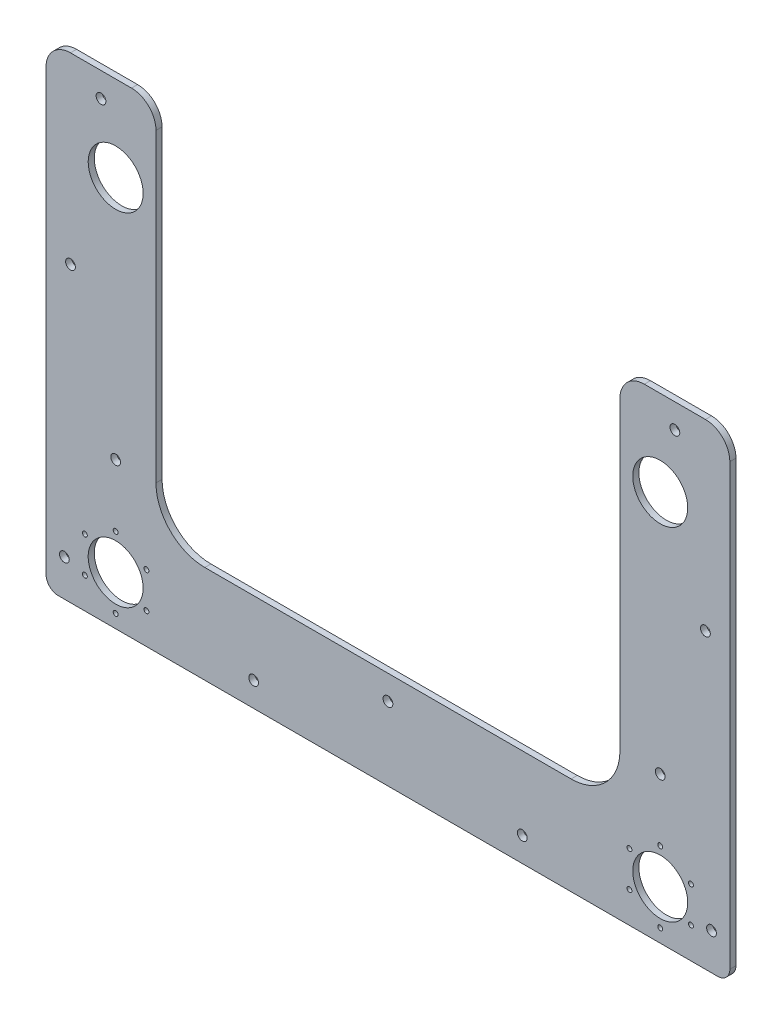
SolidWorks part; units mm, degrees
ref_plane "Front Plane" through (0, 0, 0) normal (0, 0, 1) x (1, 0, 0)
ref_plane "Top Plane" through (0, 0, 0) normal (0, 1, 0) x (1, 0, 0)
ref_plane "Right Plane" through (0, 0, 0) normal (1, 0, 0) x (0, 0, -1)
sketch "Sketch1" plane through (0, 0, 0) normal (0, 0, 1) x (1, 0, 0)
  line L5 (120.65, -152.4) -> (120.65, -6.35)
  line L6 (127, 0) -> (171.45, 0) construction
  line L7 (177.8, -6.35) -> (177.8, -222.25)
  line L10 (0, -206.2199) -> (0, -63.6275) construction
  line L11 (-54.9244, 0) -> (300.6756, 0) construction
  line L13 (12.7, -177.8) -> (95.25, -177.8)
  line L14 (12.7, -228.6) -> (171.45, -228.6)
  line L15 (141.605, -25.4) -> (141.605, -84.2822) construction
  line L16 (141.605, -25.4) -> (141.605, -127) construction
  line L17 (-141.605, -25.4) -> (-141.605, -203.2) construction
  line L18 (-141.605, -25.4) -> (-141.605, -127) construction
  line L19 (-141.605, -19.05) -> (-141.605, -77.9322) construction
  line L20 (141.605, -25.4) -> (141.605, -203.2) construction
  line L22 (-120.65, -152.4) -> (-120.65, -6.35)
  line L23 (-12.7, -177.8) -> (-95.25, -177.8)
  line L24 (-12.7, -228.6) -> (-171.45, -228.6)
  line L25 (-177.8, -6.35) -> (-177.8, -222.25)
  line L26 (-12.7, -177.8) -> (12.7, -177.8)
  line L27 (-12.7, -228.6) -> (12.7, -228.6)
  line L28 (-177.8, -6.35) -> (-177.8, 6.35)
  line L29 (-165.1, 19.05) -> (-133.35, 19.05)
  line L30 (-120.65, 6.35) -> (-120.65, -6.35)
  line L31 (120.65, 6.35) -> (120.65, -6.35)
  line L32 (177.8, -6.35) -> (177.8, 6.35)
  line L33 (165.1, 19.05) -> (133.35, 19.05)
  arc A0 (95.25, -177.8) -> (120.65, -152.4) centre (95.25, -152.4) ccw
  arc A4 (120.65, -6.35) -> (127, 0) centre (127, -6.35) cw construction
  circle A8 centre (141.605, -25.4) radius 14.2875
  circle A9 centre (141.605, -25.4) radius 38.1 construction
  arc A10 (177.8, -6.35) -> (171.45, 0) centre (171.45, -6.35) ccw construction
  arc A11 (171.45, -228.6) -> (177.8, -222.25) centre (171.45, -222.25) ccw
  arc A14 (141.605, -82.55) -> (120.9214, -78.6758) centre (141.605, -25.4) ccw construction
  arc A15 (-141.605, -82.55) -> (-120.9214, -78.6758) centre (-141.605, -25.4) cw construction
  circle A16 centre (-141.605, -25.4) radius 38.1 construction
  circle A17 centre (-141.605, -25.4) radius 14.2875
  arc A19 (-95.25, -177.8) -> (-120.65, -152.4) centre (-95.25, -152.4) cw
  circle A20 centre (141.605, -127) radius 38.1 construction
  circle A21 centre (-141.605, -127) radius 38.1 construction
  arc A23 (-171.45, -228.6) -> (-177.8, -222.25) centre (-171.45, -222.25) cw
  circle A24 centre (-141.605, -203.2) radius 14.2875
  circle A25 centre (-141.605, -184.7225) radius 1.27
  circle A26 centre (-125.603, -193.9612) radius 1.27
  circle A27 centre (-125.603, -212.4388) radius 1.27
  circle A28 centre (-141.605, -221.6775) radius 1.27
  circle A29 centre (-157.607, -212.4388) radius 1.27
  circle A30 centre (-157.607, -193.9612) radius 1.27
  circle A31 centre (157.607, -212.4388) radius 1.27
  circle A32 centre (157.607, -193.9612) radius 1.27
  circle A33 centre (141.605, -184.7225) radius 1.27
  circle A34 centre (125.603, -193.9612) radius 1.27
  circle A35 centre (125.603, -212.4388) radius 1.27
  circle A36 centre (141.605, -221.6775) radius 1.27
  circle A37 centre (141.605, -203.2) radius 14.2875
  circle A39 centre (-69.85, -215.9) radius 2.54
  circle A40 centre (69.85, -215.9) radius 2.54
  circle A42 centre (0, -190.5) radius 2.54
  circle A43 centre (-141.605, -152.4) radius 2.54
  arc A44 (-133.35, 19.05) -> (-120.65, 6.35) centre (-133.35, 6.35) cw
  arc A45 (-177.8, 6.35) -> (-165.1, 19.05) centre (-165.1, 6.35) cw
  arc A46 (133.35, 19.05) -> (120.65, 6.35) centre (133.35, 6.35) ccw
  arc A47 (177.8, 6.35) -> (165.1, 19.05) centre (165.1, 6.35) ccw
  circle A50 centre (-149.225, 6.35) radius 2.54
  circle A51 centre (141.605, -152.4) radius 2.54
  circle A53 centre (149.225, 6.35) radius 2.54
  circle A54 centre (-168.275, -209.55) radius 2.54
  circle A56 centre (168.275, -209.55) radius 2.54
  circle A58 centre (-165.1, -76.2) radius 2.54
  circle A59 centre (165.1, -76.2) radius 2.54
  point P2 (177.8, -44.45)
  point P18 (177.8, 0)
  point P23 (177.8, -228.6)
  point P24 (177.8, -228.6)
  point P31 (177.8, 0)
  point P48 (-177.8, 0)
  point P49 (-177.8, -228.6)
  point P51 (-177.8, -44.45)
  point P78 (-141.605, -203.2)
  dimension "D6" = 25.4
  dimension "D7" = 6.35
  dimension "D8" = 6.35
  dimension "D9" = 177.8
  dimension "D10" = 28.575
  dimension "D12" = 76.2
  dimension "D13" = 57.15
  dimension "D15" = 28.575
  dimension "D18" = 76.2
  dimension "D21" = 2.54
  dimension "D29" = 9.525
  dimension "D32" = 5.08
  dimension "D35" = 5.08
  dimension "D37" = 5.08
  dimension "D40" = 12.7
  dimension "D43" = 5.08
  dimension "D45" = 12.7
  dimension "D30" = 5.08
  dimension "D41" = 5.08
  dimension "D2" = 120.65
  dimension "D3" = 177.8
  dimension "D4" = 228.6
  dimension "D5" = 177.8
  dimension "D11" = 20.955
  dimension "`" = 25.4
  dimension "D14" = 57.15
  dimension "D16" = 184.15
  dimension "D17" = 101.6
  dimension "D19" = 25.4
  dimension "D20" = 107.95
  dimension "D22" = 0
  dimension "D23" = 18.4775
  dimension "D25" = 6.9225
  dimension "D26" = 19.05
  dimension "D27" = 25.4
  dimension "D28" = 25.4
  dimension "D31" = 76.2
  dimension "D33" = 12.7
  dimension "D34" = 12.7
  dimension "D36" = 12.7
  dimension "D38" = 76.2
  dimension "D39" = 19.05
  dimension "D44" = 28.575
  dimension "D24" = 6
extrude "Boss-Extrude3" add sketch "Sketch1" along normal blind 3.175
